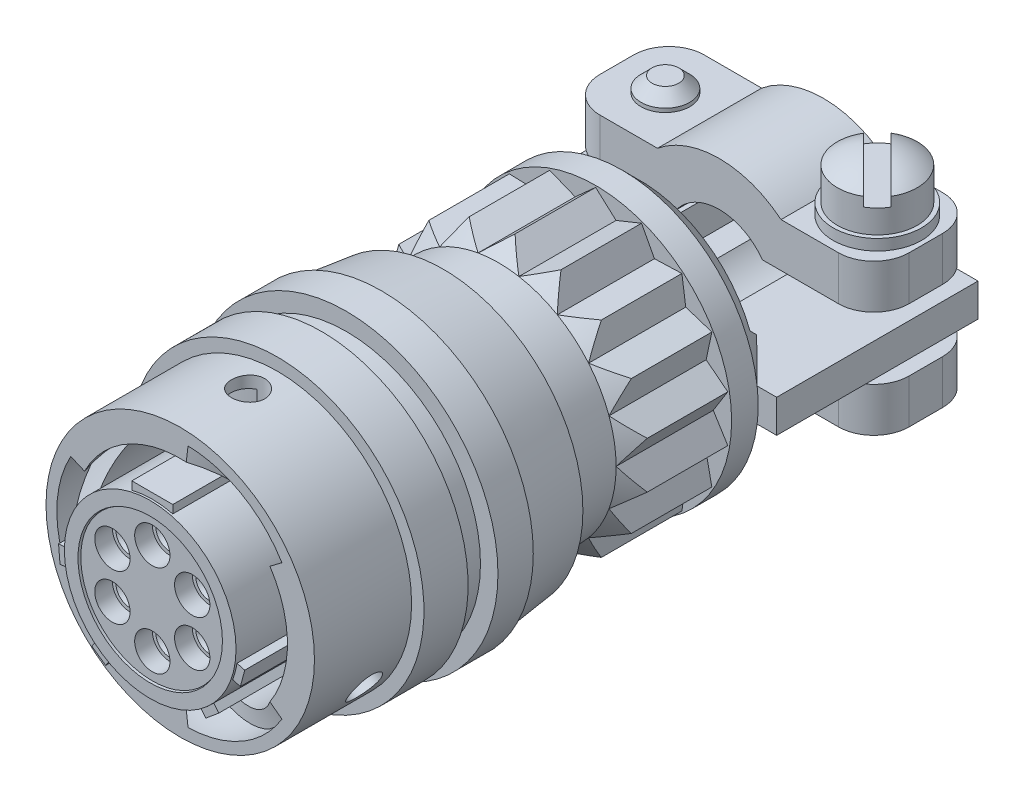
SolidWorks part; units mm, degrees
note: The reader was unsure of these and kept them because the rebuilt part matched: shared geometry of "Sketch10-6S<6>".
ref_plane "Front Plane" through (0, 0, 0) normal (0, 0, 1) x (1, 0, 0)
ref_plane "Top Plane" through (0, 0, 0) normal (0, 1, 0) x (1, 0, 0)
ref_plane "Right Plane" through (0, 0, 0) normal (1, 0, 0) x (0, 0, -1)
sketch "Sketch1" plane through (0, 0, 0) normal (1, 0, 0) x (0, 0, -1)
  line L0 (0, 0) -> (48.4124, 0) construction
  line L1 (0, 10.9093) -> (0, -10.9093) construction
  line L2 (48.4124, 3.8354) -> (48.4124, -3.8354) construction
  line L3 (48.4124, 2.3876) -> (48.4124, -2.3876) construction
  line L4 (0, 7.7089) -> (0, -7.7089) construction
  line L6 (0, 5.1943) -> (0, -5.1943) construction
  line L7 (0, 6.1722) -> (0, -6.1722) construction
  line L8 (0.1524, 5.1435) -> (0.1524, -5.1435) construction
  line L9 (21.2344, 7.1437) -> (21.2344, -7.1437) construction
  line L10 (21.2344, 7.1437) -> (20.1761, 7.1437) construction
  line L12 (23.0124, 6.35) -> (23.0124, -6.35) construction
  line L13 (0, 0) -> (7.9502, 0) construction
  line L14 (23.0124, 6.3119) -> (23.0124, -6.3119) construction
  line L15 (9.2202, 6.7437) -> (9.2202, -6.7437) construction
  line L16 (0, 8.9154) -> (0, -8.9154) construction
  point P12 (0.1524, 0)
  point P14 (7.9502, 0)
  point P21 (2.159, 0)
  point P22 (5.842, 0)
  point P25 (21.2344, 0)
  point P30 (13.8684, 0)
  point P34 (23.0124, 0)
  point P42 (9.2202, 0)
  dimension "D2" = 1.778
  dimension "D1" = 7.366
sketch "Sketch2" plane through (0, 0, 0) normal (0, 0, 1) x (1, 0, 0)
  line L0 (-11.1125, 0) -> (11.1125, 0) construction
  circle A0 centre (0, 0) radius 6.1722 construction
  circle A1 centre (0, 0) radius 6.7437 construction
  circle A2 centre (0, 0) radius 10.9093 construction
  circle A3 centre (0, 0) radius 8.9154 construction
  dimension "H" = 22.225
sketch "Sketch3" plane through (0, 0, 0) normal (1, 0, 0) x (0, 0, -1)
  line L0 (0, 0) -> (48.4124, 0) construction
  line L1 (9.7282, 6.7437) -> (9.7282, 6.35)
  line L2 (0, 6.1722) -> (9.2202, 6.1722)
  line L3 (0, 6.1722) -> (0, 5.1943)
  line L4 (0, 5.1943) -> (21.2344, 5.1943)
  line L5 (21.2344, 6.35) -> (23.0124, 6.35)
  line L6 (9.7282, 6.35) -> (13.8684, 6.35)
  line L7 (0.1524, 5.1435) -> (21.2344, 5.1435)
  line L8 (0.1524, 5.1435) -> (0.1524, 0)
  line L9 (0.1524, 0) -> (21.2344, 0)
  line L10 (21.2344, 5.1435) -> (21.2344, 0)
  line L11 (23.0124, 6.35) -> (23.0124, -6.35) construction
  line L12 (23.0124, 6.35) -> (23.0124, 6.3119)
  line L13 (21.2344, 7.1437) -> (21.2344, -7.1437) construction
  line L25 (23.0124, 6.3119) -> (21.2344, 6.3119)
  line L26 (21.2344, 6.3119) -> (21.2344, 5.1943)
  line L28 (21.2344, 6.35) -> (20.4406, 7.1437)
  line L29 (20.4406, 7.1437) -> (14.6622, 7.1437)
  line L30 (14.6622, 7.1437) -> (13.8684, 6.35)
  line L31 (9.7282, 6.7437) -> (9.2202, 6.7437)
  line L32 (13.8684, 6.35) -> (13.8684, 7.1437) construction
  line L33 (13.8684, 7.1437) -> (14.6622, 7.1437) construction
  line L35 (9.2202, 6.7437) -> (9.2202, 6.1722)
  dimension "D2" = 0.508
  dimension "D3" = 45
revolve "Revolve1" add sketch "Sketch3" angle 360 about L0
sketch "Sketch4" plane through (0, 0, 0) normal (0, 0, 1) x (1, 0, 0)
  line L0 (-1.4732, 6.5808) -> (1.4732, 6.5808)
  line L1 (0, 6.5808) -> (0, 0) construction
  line L2 (0, 0) -> (6.4872, -1.7383) construction
  line L3 (0, 0) -> (4.317, -5.1448) construction
  line L4 (0, 0) -> (-3.8522, -5.5015) construction
  line L5 (0, 0) -> (-6.6905, -0.5853) construction
  line L6 (6.645, -1.1494) -> (6.3295, -2.3271)
  line L7 (4.784, -4.753) -> (3.85, -5.5367)
  line L8 (-3.3528, -5.8512) -> (-4.3515, -5.1518)
  line L9 (-6.6374, -1.1926) -> (-6.7437, 0.0219)
  line L10 (6.645, -1.1494) -> (6.0905, -1.0008)
  line L11 (6.3295, -2.3271) -> (5.775, -2.1785)
  line L12 (4.784, -4.753) -> (4.415, -4.3132)
  line L13 (3.85, -5.5367) -> (3.481, -5.0969)
  line L14 (-3.3528, -5.8512) -> (-3.0236, -5.3809)
  line L15 (-4.3515, -5.1518) -> (-4.0223, -4.6816)
  line L16 (-6.6374, -1.1926) -> (-6.0655, -1.1426)
  line L17 (-6.7437, 0.0219) -> (-6.1718, 0.072)
  line L18 (-1.4732, 6.5808) -> (-1.4732, 5.9938)
  line L19 (1.4732, 6.5808) -> (1.4732, 5.9938)
  arc A0 (3.481, -5.0969) -> (4.415, -4.3132) centre (0, 0) ccw
  arc A1 (5.775, -2.1785) -> (6.0905, -1.0008) centre (0, 0) ccw
  circle A2 centre (0, 0) radius 6.1722 construction
  circle A3 centre (0, 0) radius 6.7437 construction
  arc A4 (-4.0223, -4.6816) -> (-3.0236, -5.3809) centre (0, 0) ccw
  circle A5 centre (0, 0) radius 6.7437 construction
  arc A6 (-6.1718, 0.072) -> (-6.0655, -1.1426) centre (0, 0) ccw
  arc A7 (1.4732, 5.9938) -> (-1.4732, 5.9938) centre (0, 0) ccw
  dimension "D1" = 2.9464
  dimension "D2" = 105
  dimension "D3" = 140
  dimension "D4" = 215
  dimension "D5" = 265
  dimension "D6" = 1.2192
extrude "Boss-Extrude1" add sketch "Sketch4" against normal up to vertex (9.2202 mm away) from vertex at -0.1524 starting at point (0, 0, -0.1524)
sketch "Sketch5" plane through (0, 0, 0) normal (1, 0, 0) x (0, 0, -1)
  line L0 (23.0124, 0) -> (0, 0) construction
  line L1 (2.159, 9.652) -> (2.159, 7.7089)
  line L3 (17.272, 7.7089) -> (17.272, 9.5885)
  line L4 (17.272, 9.5885) -> (21.082, 9.5885)
  line L5 (21.082, 9.5885) -> (21.082, 10.033)
  line L6 (2.159, 7.7089) -> (17.272, 7.7089)
  line L7 (2.159, 9.652) -> (9.144, 9.652)
  line L8 (21.082, 10.033) -> (16.637, 10.5788)
  line L9 (16.637, 10.5788) -> (16.637, 10.9093)
  line L10 (16.637, 10.9093) -> (14.097, 10.9093)
  line L11 (14.097, 10.9093) -> (14.097, 9.652)
  line L12 (14.097, 9.652) -> (12.319, 9.652)
  line L13 (12.319, 9.652) -> (12.319, 10.541)
  line L14 (12.319, 10.541) -> (9.144, 10.541)
  line L16 (9.144, 10.541) -> (9.144, 9.652)
  dimension "D5" = 6.985
  dimension "D1" = 19.304
  dimension "D3" = 21.082
  dimension "D4" = 18.923
  dimension "D6" = 3.175
  dimension "D7" = 1.778
  dimension "D8" = 2.54
  dimension "D9" = 19.177
  dimension "D10" = 7
  dimension "D11" = 3.81
  dimension "D12" = 20.066
revolve "Revolve2" add sketch "Sketch5" angle 360 about L0
sketch "Sketch6" plane through (0, 0, 0) normal (0, 1, 0) x (1, 0, 0)
  line L0 (0, 0) -> (0, 48.4124) construction
  circle A0 centre (0, 7.0358) radius 1.1938
  dimension "D1" = 2.3876
extrude "Cut-Extrude1" cut sketch "Sketch6" along normal through all
sketch "Sketch7" plane through (0, 0, -2.159) normal (0, 0, 1) x (1, 0, 0)
  circle A0 centre (0, 0) radius 7.7089 construction
  circle A1 centre (0, 0) radius 7.7089
  point P3 (-7.7089, 0)
curve "Helix/Spiral1" pitch 19.5072 height 4.8768 turns 0.25
ref_plane "Plane2" through (-7.7089, 0, -2.159) normal (0, 0.9276, -0.3736) x (-1, 0, 0)
sketch "Sketch8" plane through (-7.7089, 0, -2.159) normal (0, 0.9276, -0.3736) x (-1, 0, 0)
  line L0 (-7.7089, 0) -> (0, 0) construction
  line L1 (0, 0) -> (1.164, 0) construction
  line L2 (-0.1185, 1.3462) -> (1.0613, 1.3462)
  line L3 (1.164, 0) -> (1.164, 2.3275) construction
  line L4 (-0.1185, -1.3462) -> (1.0613, -1.3462)
  arc A0 (1.0613, -1.3462) -> (1.0613, 1.3462) centre (-7.7089, 0) ccw
  arc A1 (-0.1185, -1.3462) -> (-0.1185, 1.3462) centre (-7.7089, 0) ccw
  dimension "GG" = 2.6924
sweep "Cut-Sweep1" cut profiles "Sketch8" path "Helix/Spiral1"
pattern_circular "CirPattern1" count 3 over 360 about axis through (0, 0, -23.0124) along (0, 0, -1) of "Cut-Extrude1", "Cut-Sweep1"
sketch "Sketch9" plane through (0, 0, 0) normal (1, 0, 0) x (0, 0, -1)
  line L0 (18.3134, 8.4582) -> (18.3134, 7.1437)
  line L1 (18.3134, 7.1437) -> (32.0294, 7.1437)
  line L2 (32.0294, 7.1437) -> (32.0294, 3.8354)
  line L3 (32.0294, 3.8354) -> (35.2044, 3.8354)
  line L4 (0, 0) -> (48.4124, 0) construction
  line L5 (18.3134, 8.4582) -> (32.0294, 8.4582)
  line L6 (33.9344, 9.779) -> (35.2044, 8.509)
  line L7 (32.0294, 9.779) -> (33.9344, 9.779)
  line L8 (35.2044, 8.509) -> (35.2044, 3.8354)
  line L9 (32.0294, 9.779) -> (32.0294, 8.4582)
  dimension "D1" = 16.891
  dimension "D2" = 13.716
  dimension "D3" = 16.9164
  dimension "D4" = 19.558
  dimension "D5" = 17.018
  dimension "D6" = 45
  dimension "D7" = 13.716
  dimension "D11" = 13.208
revolve "Revolve3" add sketch "Sketch9" angle 360 about L4
sketch "Sketch10" plane through (0, 0, -32.0294) normal (0, 0, 1) x (1, 0, 0)
  line L0 (0, 8.4582) -> (0, 0) construction
  line L1 (0, 0) -> (-1.4688, 8.3297) construction
  line L2 (0, 0) -> (1.4688, 8.3297) construction
  line L3 (-1.4688, 8.3297) -> (0, 9.652)
  line L4 (0, 9.652) -> (1.4688, 8.3297)
  line L5 (0, 8.4582) -> (0, 9.652) construction
  circle A0 centre (0, 0) radius 8.4582 construction
  arc A1 (1.4688, 8.3297) -> (-1.4688, 8.3297) centre (0, 0) ccw
  circle A3 centre (0, 0) radius 9.779 construction
  dimension "D1" = 20
  dimension "D2" = 0.127
extrude "Boss-Extrude2" add sketch "Sketch10" along normal blind 6.985
pattern_circular "CirPattern2" count 18 over 360 about axis through (0, 0, 0) along (0, 0, 1) of "Boss-Extrude2"
sketch "Sketch11" plane through (0, 0, 0) normal (1, 0, 0) x (0, 0, -1)
  line L0 (32.0294, 0) -> (0, 0) construction
  line L1 (25.0444, 9.652) -> (25.0444, 8.4582)
  line L2 (25.0444, 8.4582) -> (26.2382, 9.652)
  line L3 (25.0444, 9.652) -> (32.0294, 9.652) construction
  line L4 (26.2382, 9.652) -> (25.0444, 9.652)
  dimension "D1" = 45
revolve "Cut-Revolve1" cut sketch "Sketch11" angle 360 about L0
sketch "Sketch12" plane through (0, 0, -35.2044) normal (0, 0, -1) x (-1, 0, 0)
  line L0 (0, 3.8354) -> (0, -3.8354) construction
  line L1 (-11.1125, 1.1875) -> (-3.8354, 1.1875)
  line L2 (-11.1125, 1.1875) -> (-11.1125, -1.1875)
  line L3 (-11.1125, -1.1875) -> (-3.8354, -1.1875)
  line L4 (-3.8354, 1.1875) -> (-3.8354, -1.1875)
  line L5 (3.8354, 1.1875) -> (3.8354, -1.1875)
  line L6 (11.1125, -1.1875) -> (3.8354, -1.1875)
  line L7 (11.1125, 1.1875) -> (11.1125, -1.1875)
  line L8 (11.1125, 1.1875) -> (3.8354, 1.1875)
  line L9 (-11.1125, 0) -> (11.1125, 0) construction
  circle A0 centre (0, 0) radius 3.8354 construction
  dimension "D1" = 2.3749
extrude "Boss-Extrude3" add sketch "Sketch12" along normal up to vertex (13.208 mm away) and the other way up to vertex (1.27 mm away) up to point (0, 0, -48.4124) other way up to point (0, 9.779, -33.9344)
chamfer "Chamfer1" distance 1.905 angle 45 4 edges at (-6.1306, 1.1875, -35.2044) (-6.1306, -1.1875, -35.2044) (6.1306, -1.1874, -35.2044) (6.1306, 1.1874, -35.2044)
sketch "Sketch13" plane through (0, 0, 0) normal (0, 1, 0) x (1, 0, 0)
  line L0 (-7.62, 44.6659) -> (7.62, 44.6659) construction
  line L1 (0, 44.6659) -> (0, 48.4124) construction
  circle A0 centre (7.62, 44.6659) radius 1.7526
  circle A1 centre (-7.62, 44.6659) radius 1.7526
  dimension "D3" = 3.5052
  dimension "D1" = 15.24
  dimension "D2" = 3.7465
extrude "Cut-Extrude2" cut sketch "Sketch13" against normal up to next (1.1874 mm away) and the other way up to next (1.1874 mm away)
sketch "Sketch14" plane through (0, 0, -48.4124) normal (0, 0, -1) x (-1, 0, 0)
  line L0 (-11.1125, 2.2479) -> (-11.1125, 5.4229)
  line L1 (-11.1125, 1.1875) -> (-11.1125, -1.1875) construction
  line L2 (-11.1125, 2.2479) -> (-3.1076, 2.2479)
  line L3 (-11.1125, 5.4229) -> (-4.4427, 5.4229)
  line L4 (0, 0) -> (0, 3.8354) construction
  line L5 (11.1125, 5.4229) -> (4.4427, 5.4229)
  line L6 (11.1125, 2.2479) -> (3.1076, 2.2479)
  line L7 (11.1125, 2.2479) -> (11.1125, 5.4229)
  line L8 (0, 3.8354) -> (0, 7.0104) construction
  circle A0 centre (0, 0) radius 3.8354 construction
  arc A1 (3.1076, 2.2479) -> (-3.1076, 2.2479) centre (0, 0) ccw
  arc A3 (4.4427, 5.4229) -> (-4.4427, 5.4229) centre (0, 0) ccw
  dimension "D1" = 3.175
  dimension "D2" = 4.7625
extrude "Boss-Extrude4" add sketch "Sketch14" against normal blind 7.493 separate body
sketch "Sketch15" plane through (0, 0, 0) normal (0, 1, 0) x (1, 0, 0)
  line L0 (3.1076, 48.4124) -> (11.1125, 48.4124) construction
  line L1 (11.1125, 48.4124) -> (11.1125, 40.9194) construction
  line L2 (11.1125, 40.9194) -> (3.1076, 40.9194) construction
  line L4 (-11.1125, 48.4124) -> (-3.1076, 48.4124) construction
  line L6 (-3.1076, 40.9194) -> (-11.1125, 40.9194) construction
  line L7 (-11.1125, 40.9194) -> (-11.1125, 48.4124) construction
  line L8 (8.5725, 48.4124) -> (11.1125, 48.4124)
  line L9 (11.1125, 48.4124) -> (11.1125, 45.8724)
  line L10 (11.1125, 40.9194) -> (8.5725, 40.9194)
  line L11 (11.1125, 43.4594) -> (11.1125, 40.9194)
  line L12 (-11.1125, 48.4124) -> (-8.5725, 48.4124)
  line L13 (-11.1125, 45.8724) -> (-11.1125, 48.4124)
  line L14 (-8.5725, 40.9194) -> (-11.1125, 40.9194)
  line L15 (-11.1125, 40.9194) -> (-11.1125, 43.4594)
  arc A0 (11.1125, 45.8724) -> (8.5725, 48.4124) centre (8.5725, 45.8724) ccw
  circle A1 centre (-7.62, 44.6659) radius 1.7526
  circle A2 centre (-7.62, 44.6659) radius 1.7526
  circle A3 centre (7.62, 44.6659) radius 1.7526
  circle A4 centre (7.62, 44.6659) radius 1.7526
  arc A5 (8.5725, 40.9194) -> (11.1125, 43.4594) centre (8.5725, 43.4594) ccw
  arc A6 (-8.5725, 48.4124) -> (-11.1125, 45.8724) centre (-8.5725, 45.8724) ccw
  arc A7 (-11.1125, 43.4594) -> (-8.5725, 40.9194) centre (-8.5725, 43.4594) ccw
  dimension "D3" = 2.54
  dimension "D1" = 0
  dimension "D2" = 0
extrude "Cut-Extrude3" cut sketch "Sketch15" along normal through all
ref_plane "Plane1" through (0, 0, -44.6659) normal (0, 0, 1) x (1, 0, 0)
sketch "Sketch16" plane through (0, 0, -44.6659) normal (0, 0, 1) x (1, 0, 0)
  line L0 (7.62, 0) -> (7.62, 6.2103) construction
  line L1 (9.3726, 5.4229) -> (5.8674, 5.4229) construction
  line L2 (5.7404, 6.2103) -> (4.445, 6.2103)
  line L3 (5.7404, 6.2103) -> (5.7404, 5.4229)
  line L4 (5.7404, 5.4229) -> (4.445, 5.4229)
  line L5 (4.445, 6.2103) -> (4.445, 5.4229)
  dimension "D1" = 3.7592
  dimension "D2" = 6.35
  dimension "D3" = 0.7874
revolve "Revolve4" add sketch "Sketch16" angle 360 about L0
sketch "Sketch17" plane through (0, 0, -44.6659) normal (0, 0, 1) x (1, 0, 0)
  line L0 (7.62, 6.2103) -> (7.62, 0) construction
  line L1 (7.62, 9.5631) -> (7.62, -6.4897)
  line L2 (7.62, -6.4897) -> (6.6611, -6.4897)
  line L3 (6.6611, -6.4897) -> (5.8674, -5.696)
  line L4 (5.8674, -5.696) -> (5.8674, 6.2103)
  line L5 (5.8674, 6.2103) -> (4.7498, 6.2103)
  line L6 (4.7498, 6.2103) -> (4.7498, 8.5573)
  arc A0 (7.62, 9.5631) -> (4.7498, 8.5573) centre (7.62, 4.9651) ccw
  point P10 (5.8674, 1.1874)
  dimension "D1" = 5.7404
  dimension "D2" = 3.3528
  dimension "D3" = 0.7937
  dimension "D4" = 45
  dimension "D5" = 12.7
  dimension "D6" = 1.0058
revolve "Revolve5" add sketch "Sketch17" angle 360 about L0
sketch "Sketch18" plane through (0, 6.2103, 0) normal (0, -1, 0) x (1, 0, 0)
  line L0 (8.1111, -45.157) -> (7.1289, -44.1748) construction
  line L1 (5.0994, -46.2043) -> (6.0816, -47.1865)
  line L2 (5.0994, -46.2043) -> (9.1584, -42.1453)
  line L3 (9.1584, -42.1453) -> (10.1406, -43.1275)
  line L4 (6.0816, -47.1865) -> (10.1406, -43.1275)
  line L5 (5.8674, -44.6659) -> (4.7498, -44.6659) construction
  circle A0 centre (7.62, -44.6659) radius 2.8702 construction
  dimension "D1" = 1.3891
  dimension "D2" = 45
extrude "Cut-Extrude4" cut sketch "Sketch18" against normal through all from offset 1.6764 offset against normal yes
pattern_circular "CirPattern3" count 2 over 360 about axis through (0, 0, 0) along (0, 0, 1) of bodies 184 180 179 164 181
sketch "Sketch10-6S" plane through (0, 0, -0.1524) normal (0, 0, 1) x (1, 0, 0)
  circle A0 centre (0, 3.302) radius 1.27
  circle A1 centre (2.8702, 1.651) radius 1.27
  circle A2 centre (2.8702, -1.651) radius 1.27
  circle A3 centre (0, -3.302) radius 1.27
  circle A4 centre (-2.8702, -1.651) radius 1.27
  circle A5 centre (-2.8702, 1.651) radius 1.27
  dimension "D1" = 2.54
  dimension "D2" = 0
  dimension "D3" = 3.302
  dimension "D4" = 2.8702
  dimension "D5" = 1.651
  dimension "D6" = 2.8702
  dimension "D7" = 1.651
  dimension "D8" = 0
  dimension "D9" = 3.302
  dimension "D10" = 2.8702
  dimension "D11" = 1.651
  dimension "D12" = 2.8702
  dimension "D13" = 1.651
extrude "Cut-Extrude10-6S" cut sketch "Sketch10-6S" against normal up to vertex (7.7978 mm away) up to point (0, 0, -7.9502)
extrude "Extrude-Thin10-6S" add sketch "Sketch10-6S<6>" against normal offset from surface (22.86 mm away) 3.048 from offset 1.27 thin up to face at (5.1435, 0, -21.2344) offset beyond the face yes thin type one direction reverse wall 0.635 offset against normal yes
sketch "Sketch10-6S<6>" plane through (0, 0, -0.1524) normal (0, 0, 1) x (1, 0, 0) same geometry as "Sketch10-6S"
chamfer "Chamfer10-6S" distance 0.381 angle 45 6 edges at (-2.2352, 1.651, -1.4224) (-2.2352, -1.651, -1.4224) (0.635, -3.302, -1.4224) (3.5052, -1.651, -1.4224) (3.5052, 1.651, -1.4224) (0.635, 3.302, -1.4224)
equation "\"D3@Helix/Spiral1\" = \"N@Sketch1\" - \"D@Sketch1\" - \"E@Sketch1\" + ( \"D1@Sketch6\" / 2 ) "
equation "\"D1@CirPattern2\" = 360 / \"D1@Sketch10\""
